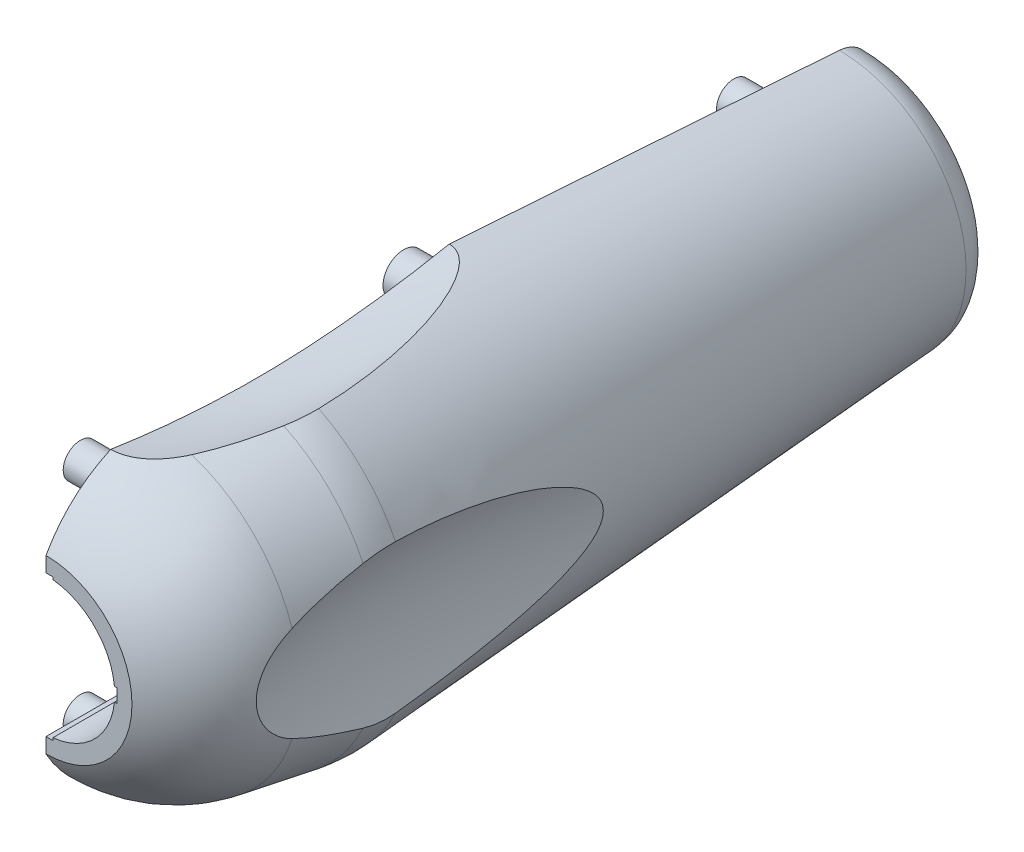
SolidWorks part; units mm, degrees
ref_plane "Ön Düzlem" through (0, 0, 0) normal (0, 0, 1) x (1, 0, 0)
ref_plane "Üst Düzlem" through (0, 0, 0) normal (0, 1, 0) x (1, 0, 0)
ref_plane "Sağ Düzlem" through (0, 0, 0) normal (1, 0, 0) x (0, 0, -1)
sketch "Sketch1" plane through (0, 0, 0) normal (0, 0, 1) x (1, 0, 0)
  circle A0 centre (0, 0) radius 5
  circle A1 centre (0, 0) radius 11.25
  dimension "D1" = 10
  dimension "D2" = 22.5
extrude "Boss-Extrude1" add sketch "Sketch1" along normal blind 51
sketch "Sketch2" plane through (0, 0, 0) normal (0, 0, -1) x (-1, 0, 0)
  circle A0 centre (0, 0) radius 11.25
extrude "Boss-Extrude2" add sketch "Sketch2" along normal blind 9
sketch "Sketch3" plane through (0, 0, -9) normal (0, 0, -1) x (-1, 0, 0)
  line L0 (-2, 4.5) -> (-3, 3.5)
  line L1 (-3, 2.5) -> (3, 2.5)
  line L2 (-3, 2.5) -> (-3, 3.5)
  line L3 (-2, 4.5) -> (2, 4.5)
  line L4 (3, 2.5) -> (3, 3.5)
  line L5 (3, 3.5) -> (2, 4.5)
  point P4 (0, 2.5)
  dimension "D1" = 6
  dimension "D3" = 2.5
  dimension "D4" = 4
  dimension "D5" = 45
extrude "Cut-Extrude1" cut sketch "Sketch3" against normal blind 6
sketch "Sketch4" plane through (0, 0, -9) normal (0, 0, -1) x (-1, 0, 0)
  line L1 (-5, -1) -> (5, -1)
  line L2 (-5, -1) -> (-5, -3.5)
  line L3 (-5, -3.5) -> (5, -3.5)
  line L4 (5, -1) -> (5, -3.5)
  point P4 (0, -3.5)
  dimension "D1" = 10
  dimension "D2" = 2.5
  dimension "D3" = 1
extrude "Cut-Extrude2" cut sketch "Sketch4" against normal blind 5 from offset 2.5 offset against normal yes
sketch "Sketch5" plane through (0, 0, -9) normal (0, 0, -1) x (-1, 0, 0)
  circle A0 centre (0, -3.5) radius 2.5
  dimension "D1" = 5
  dimension "D2" = 3.5
extrude "Cut-Extrude3" cut sketch "Sketch5" against normal blind 7.5
sketch "Sketch6" plane through (0, 0, 51) normal (0, 0, 1) x (1, 0, 0)
  line L0 (0.5, 4.9) -> (-0.5, 4.9)
  line L1 (-4.9, 0.5) -> (-5.15, 0.5)
  line L2 (-4.9, 0.5) -> (-4.9, -0.5)
  line L3 (-4.9, -0.5) -> (-5.15, -0.5)
  line L4 (-5.15, 0.5) -> (-5.15, -0.5)
  line L5 (0.5, 4.9) -> (0.5, 5.15)
  line L6 (0.5, 5.15) -> (-0.5, 5.15)
  line L7 (-0.5, 4.9) -> (-0.5, 5.15)
  line L8 (4.9, -0.5) -> (4.9, 0.5)
  line L9 (4.9, -0.5) -> (5.15, -0.5)
  line L10 (5.15, -0.5) -> (5.15, 0.5)
  line L11 (4.9, 0.5) -> (5.15, 0.5)
  line L12 (-0.5, -4.9) -> (0.5, -4.9)
  line L13 (-0.5, -4.9) -> (-0.5, -5.15)
  line L14 (-0.5, -5.15) -> (0.5, -5.15)
  line L15 (0.5, -4.9) -> (0.5, -5.15)
  point P4 (-4.9, 0)
  point P21 (0, 0)
  dimension "D1" = 1
  dimension "D2" = 0.25
  dimension "D3" = 4.9
  dimension "D4" = 4
extrude "Cut-Extrude4" cut sketch "Sketch6" against normal blind 10
sketch "Sketch7" plane through (0, 0, 51) normal (0, 0, 1) x (1, 0, 0)
  line L0 (-11.25, 11.25) -> (11.25, -11.25) construction
  line L1 (-11.25, 11.25) -> (11.25, 11.25)
  line L2 (-11.25, 11.25) -> (-11.25, -11.25)
  line L3 (-11.25, -11.25) -> (11.25, -11.25)
  line L4 (11.25, 11.25) -> (11.25, -11.25)
  circle A0 centre (0, 0) radius 7.5
  point P4 (0, 0)
  dimension "D3" = 15
  dimension "D1" = 22.5
  dimension "D2" = 22.5
extrude "Boss-Extrude3" add sketch "Sketch7" against normal blind 55
sketch "Sketch11" plane through (0, 0, 51) normal (0, 0, 1) x (1, 0, 0)
  circle A0 centre (0, 0) radius 5.5
  circle A1 centre (0, 0) radius 6.25
  dimension "D1" = 12.5
  dimension "D2" = 11
extrude "Boss-Extrude4" add sketch "Sketch11" along normal blind 5
thread "Thread1" pitch 0.6 method extrude profile "Thread Profile1" start angle 0, offset 1, length 6, pitch 0.6, diameter 11
ref_plane "Plane1" through (-5.5, 0, 57) normal (0, -1, 0) x (-1, 0, 0)
sketch "Thread Profile1" plane through (-5.5, 0, 57) normal (0, -1, 0) x (-1, 0, 0)
  line L0 (0, 0) -> (0, 0.6) construction
  line L11 (0, 0) -> (0, 0.525)
  line L12 (0, 0.525) -> (-0.3248, 0.3375)
  line L13 (-0.3248, 0.3375) -> (-0.3248, 0.1875)
  line L15 (-0.3248, 0.1875) -> (0, 0)
  line L17 (-0.3248, 0.2625) -> (0, 0.2625) construction
  point P2 (0, 0)
  dimension "Pitch" = 0.6
  dimension "Profile_Angle" = 60
  dimension "Profile_Land" = 0.15
  dimension "Profile_Height" = 0.3248
sketch "Sketch14" plane through (11.25, 0, 0) normal (1, 0, 0) x (0, 0, -1)
  line L1 (-70.4093, 18.7396) -> (-55.9318, 18.7396)
  line L2 (-70.4093, 18.7396) -> (-70.4093, -13.801)
  line L3 (-70.4093, -13.801) -> (-55.9318, -13.801)
  line L4 (-55.9318, 18.7396) -> (-55.9318, -13.801)
extrude "Cut-Extrude5" cut sketch "Sketch14" against normal blind 30
sketch "Sketch15" plane through (0, 0, 0) normal (0, 1, 0) x (1, 0, 0)
  line L0 (-9, 9.75) -> (-12.3215, -37.75)
  line L1 (-12.3215, -37.75) -> (-9, -57.75)
  line L2 (11.25, 9) -> (-11.25, 9) construction
  line L3 (-9, 9.75) -> (-54, 9.75)
  line L4 (-54, 9.75) -> (-54, -633.78)
  line L5 (0, 0) -> (0, 16.5551) construction
  line L6 (-9, -57.75) -> (-13.7201, -57.75)
  line L7 (-13.7201, -57.75) -> (-54, -633.78)
  dimension "D1" = 9
  dimension "D2" = 0.75
  dimension "D3" = 45
  dimension "D4" = 86
  dimension "D5" = 47.5
  dimension "D6" = 67.5
revolve "Cut-Revolve2" cut sketch "Sketch15" angle 360 about L5
ref_plane "Plane2" through (0, 22.25, 0) normal (0, 1, 0) x (1, 0, 0)
sketch "Sketch17" plane through (0, 22.25, 0) normal (0, 1, 0) x (1, 0, 0)
  line L0 (0, 0) -> (0, -1000) construction
  line L1 (0, 8.75) -> (-7.5, -8.75) construction
  line L2 (-7.5, -8.75) -> (7.5, -8.75) construction
  line L3 (7.5, -8.75) -> (-12.5, -35.75) construction
  line L4 (-12.5, -35.75) -> (12.5, -35.75) construction
  line L5 (12.5, -35.75) -> (-7.5, -62.75) construction
  line L6 (-7.5, -62.75) -> (7.5, -62.75) construction
  line L7 (7.5, -62.75) -> (0, -80.25) construction
  line L8 (0, 8.75) -> (0, -80.25)
  spline S0 degree 3 poles (0, 8.75) (-6.8374, -4.8333) (-18.1626, -35.75) (-6.8374, -66.6667) (0, -80.25) knots 0 0 0 0 0.5 1 1 1 1
  point P5 (0, -8.75)
  point P12 (0, -35.75)
  point P13 (0, -62.75)
  dimension "D1" = 1000
  dimension "D2" = 17.5
  dimension "D3" = 17.5
  dimension "D4" = 27
  dimension "D5" = 27
  dimension "D6" = 15
  dimension "D7" = 25
  dimension "D8" = 15
  dimension "D9" = 8.75
revolve "Cut-Revolve3" cut sketch "Sketch17" angle 360 about L8
pattern_circular "CirPattern1" count 4 over 360 about axis through (0, 0, 56) along (0, 0, -1) of "Cut-Revolve3"
fillet "Fillet1" radius 10 1 edges at (10.121, 0, 51)
fillet "Fillet2" radius 10 4 edges at (-8.7126, 8.7126, 37.75) (-8.7126, -8.7126, 37.75) (8.7126, -8.7126, 37.75) (8.7126, 8.7126, 37.75)
fillet "Fillet5" radius 2.5 1 edges at (-9.0524, 0, -9)
sketch "Sketch19" plane through (0, 0, -9) normal (0, 0, -1) x (-1, 0, 0)
  line L1 (17.1805, 14.5318) -> (0, 14.5318)
  line L2 (17.1805, 14.5318) -> (17.1805, -14.9656)
  line L3 (17.1805, -14.9656) -> (0, -14.9656)
  line L4 (0, 14.5318) -> (0, -14.9656)
  point P4 (17.1805, -14.9656)
extrude "Cut-Extrude6" cut sketch "Sketch19" against normal blind 60
sketch "Sketch20" plane through (0, 0, 0) normal (-1, 0, 0) x (0, 0, 1)
  line L0 (51, 6.25) -> (51, -6.25) construction
  line L1 (63.4883, 15.6033) -> (51, 15.6033)
  line L2 (63.4883, 15.6033) -> (63.4883, -20.0584)
  line L3 (63.4883, -20.0584) -> (51, -20.0584)
  line L4 (51, 15.6033) -> (51, -20.0584)
  point P4 (52.626, -20.0584)
extrude "Cut-Extrude7" cut sketch "Sketch20" against normal blind 10 and the other way blind 10
sketch "Sketch21" plane through (0, 0, 0) normal (-1, 0, 0) x (0, 0, 1)
  line L1 (0, 0) -> (18.7859, 0) construction
  circle A0 centre (-2, 7) radius 1.25
  circle A1 centre (22, 8) radius 1.5
  circle A2 centre (45.5, 8) radius 1.25
  circle A3 centre (45.5, -8) radius 1.25
  circle A4 centre (22, -8) radius 1.5
  dimension "D1" = 2.5
  dimension "D2" = 3
  dimension "D3" = 2.5
  dimension "D4" = 7
  dimension "D5" = 8
  dimension "D6" = 8
  dimension "D7" = 2
  dimension "D8" = 22
  dimension "D9" = 23.5
extrude "Boss-Extrude5" add sketch "Sketch21" along normal blind 3
